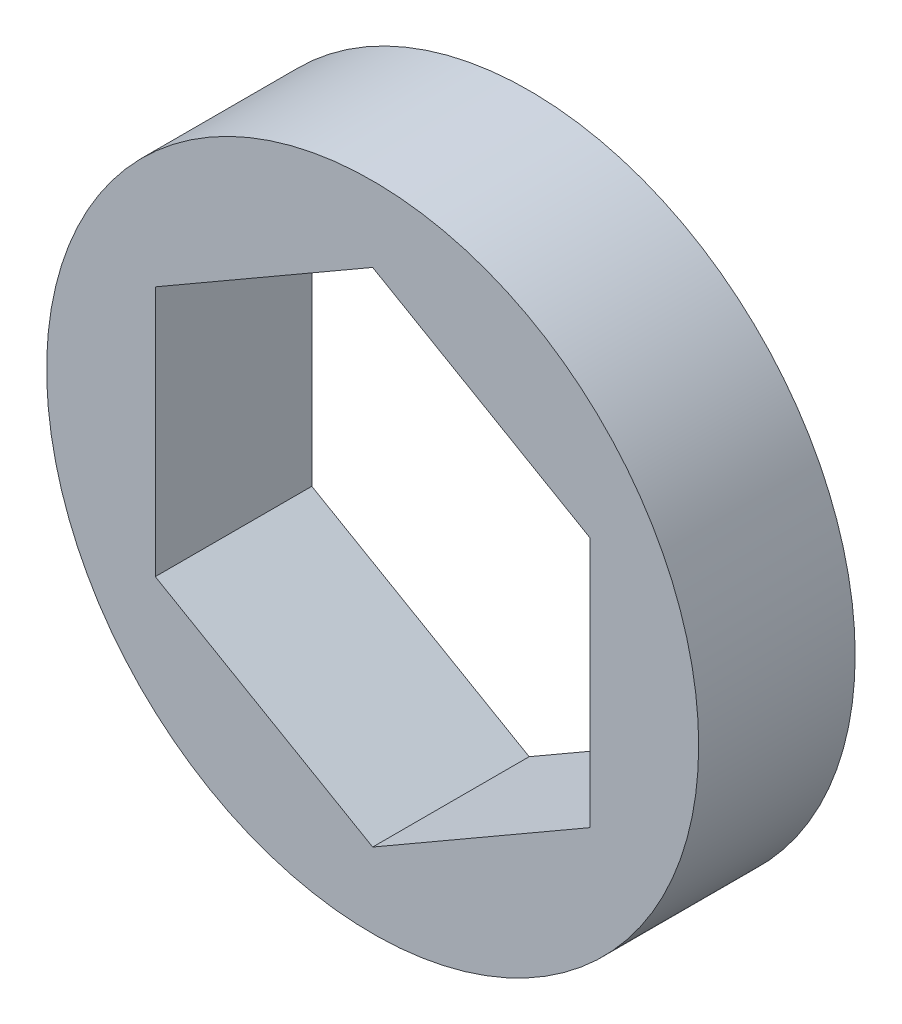
SolidWorks part; units mm, degrees
material "Nylon 101"
ref_plane "Front Plane" through (0, 0, 0) normal (0, 0, 1) x (1, 0, 0)
ref_plane "Top Plane" through (0, 0, 0) normal (0, 1, 0) x (1, 0, 0)
ref_plane "Right Plane" through (0, 0, 0) normal (1, 0, 0) x (0, 0, -1)
sketch "Sketch1" plane through (0, 0, 0) normal (0, 0, 1) x (1, 0, 0)
  line L1 (6.35, 3.6662) -> (0, 7.3323)
  line L2 (0, 7.3323) -> (-6.35, 3.6662)
  line L3 (-6.35, 3.6662) -> (-6.35, -3.6662)
  line L4 (-6.35, -3.6662) -> (0, -7.3323)
  line L5 (0, -7.3323) -> (6.35, -3.6662)
  line L6 (6.35, -3.6662) -> (6.35, 3.6662)
  circle A0 centre (0, 0) radius 6.35 construction
  circle A1 centre (0, 0) radius 9.525
  dimension "D1" = 12.7
  dimension "D2" = 19.05
extrude "Boss-Extrude1" add sketch "Sketch1" along normal blind 4.572
